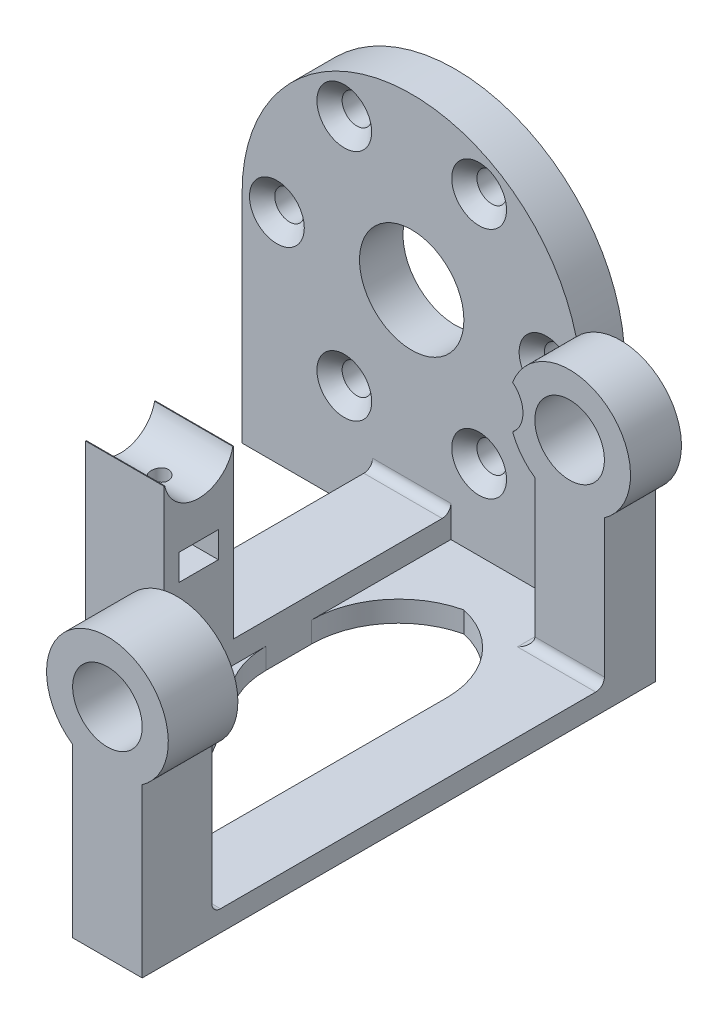
SolidWorks part; units mm, degrees
ref_plane "Front Plane" through (0, 0, 0) normal (0, 0, 1) x (1, 0, 0)
ref_plane "Top Plane" through (0, 0, 0) normal (0, 1, 0) x (1, 0, 0)
ref_plane "Right Plane" through (0, 0, 0) normal (1, 0, 0) x (0, 0, -1)
sketch "Sketch5" plane through (0, 0, 0) normal (0, 0, 1) x (1, 0, 0)
  line L0 (0, 0) -> (0, 15.5) construction
  circle A0 centre (0, 0) radius 19.5
  circle A1 centre (-7.75, 13.4234) radius 1.5
  circle A2 centre (0, 0) radius 6
  circle A3 centre (7.75, 13.4234) radius 1.5
  circle A4 centre (15.5, 0) radius 1.5
  circle A5 centre (7.75, -13.4234) radius 1.5
  circle A6 centre (-7.75, -13.4234) radius 1.5
  circle A7 centre (-15.5, 0) radius 1.5
  point P18 (0, 0)
  dimension "D2" = 3
  dimension "D3" = 39
  dimension "D4" = 12
  dimension "D1" = 15.5
  dimension "D5" = 6
extrude "Boss-Extrude1" add sketch "Sketch5" along normal blind 5
hole_wizard "CSK for M3 Flat Head Machine Screw1" positions "Sketch7" profile "Sketch6" countersink size "M3" standard "ANSI Metric" end condition through all
sketch "Sketch7" plane through (0, 0, 5) normal (0, 0, 1) x (1, 0, 0)
  point P0 (-15.5, 0)
  point P3 (-7.75, 13.4234)
  point P6 (7.75, 13.4234)
  point P9 (15.5, 0)
  point P12 (7.75, -13.4234)
  point P15 (-7.75, -13.4234)
sketch "Sketch6" plane through (-15.5, 0, 5) normal (1, 0, 0) x (0, -1, 0)
  line L0 (0, 0) -> (0, 5)
  line L1 (0, 5) -> (1.7, 5)
  line L2 (1.7, 5) -> (1.7, 1.45)
  line L3 (1.7, 1.45) -> (3.15, 0)
  line L5 (3.15, 0) -> (0, 0)
  line L6 (-1.7, 1.45) -> (-3.15, 0) construction
  line L11 (0, -6.35) -> (0, 107.95) construction
  dimension "Thru Hole Dia." = 3.4
  dimension "Thru Hole Depth" = 5
  dimension "Near C'Sink Dia." = 6.3
  dimension "Near C'Sink Angle" = 90
sketch "Sketch8" plane through (0, 0, 5) normal (0, 0, 1) x (1, 0, 0)
  line L0 (-19.5, 0) -> (-19.5, -25)
  line L1 (-19.5, -25) -> (19.5, -25)
  line L2 (19.5, -25) -> (19.5, 0)
  circle A0 centre (0, 0) radius 19.5 construction
  arc A1 (-19.5, 0) -> (19.5, 0) centre (0, 0) ccw
  dimension "D1" = 25
extrude "Boss-Extrude2" add sketch "Sketch8" against normal up to surface (5 mm away) up to face at (-13.8, 0, 0)
sketch "Sketch9" plane through (0, 0, 5) normal (0, 0, 1) x (1, 0, 0)
  line L0 (-19.5, -25) -> (19.5, -25) construction
  line L4 (-4.5, -20) -> (-4.5, -25)
  line L5 (4.5, -20) -> (-4.5, -25) construction
  line L6 (4.5, -25) -> (-4.5, -20) construction
  line L7 (-19.5, -25) -> (0, -22.5) construction
  line L8 (0, -22.5) -> (19.5, -25) construction
  line L9 (-4.5, -25) -> (4.5, -25)
  line L10 (-4.5, -20) -> (4.5, -20)
  line L11 (4.5, -20) -> (4.5, -25)
  point P0 (0, -22.5)
  dimension "D1" = 5
  dimension "D2" = 9
extrude "Boss-Extrude3" add sketch "Sketch9" along normal blind 32.9817
sketch "Sketch10" plane through (0.3712, -20, 0) normal (0, 1, 0) x (1, 0, 0)
  line L1 (-4.8712, -37.9817) -> (4.1288, -37.9817)
  line L2 (-4.8712, -37.9817) -> (-4.8712, -29.9817)
  line L3 (-4.8712, -29.9817) -> (4.1288, -29.9817)
  line L4 (4.1288, -37.9817) -> (4.1288, -29.9817)
  line L6 (-4.8712, -37.9817) -> (-4.8712, -5) construction
  line L7 (4.1288, -37.9817) -> (4.1288, -5) construction
  dimension "D1" = 8
extrude "Boss-Extrude4" add sketch "Sketch10" along normal blind 24
sketch "Sketch11" plane through (-4.5, 0, 0) normal (-1, 0, 0) x (0, 0, 1)
  line L0 (29.9817, 4) -> (29.9817, -20) construction
  line L2 (29.9817, 4) -> (37.9817, 4) construction
  line L3 (37.9817, 4) -> (37.9817, -25) construction
  line L4 (29.9817, 0) -> (27.1369, 2.0822)
  line L5 (27.1369, 2.0822) -> (27.3574, 4.8482)
  line L6 (27.3574, 4.8482) -> (32.7492, 5.4696)
  line L7 (32.7492, 5.4696) -> (41.4483, 5.0286)
  line L8 (41.4483, 5.0286) -> (40.8237, 2.383)
  line L9 (40.8237, 2.383) -> (37.9817, 0)
  line L10 (29.9817, -0.8) -> (30.0625, -0.8)
  line L11 (37.9009, -0.8) -> (37.9817, -0.8)
  line L12 (37.9817, 0) -> (37.9817, -0.8)
  line L13 (29.9817, -0.8) -> (29.9817, 0)
  arc A0 (30.0625, -0.8) -> (37.9009, -0.8) centre (33.9817, 0) ccw
  dimension "D1" = 0.8
extrude "Cut-Extrude1" cut sketch "Sketch11" against normal blind 20
sketch "Sketch12" plane through (0, -0.8, 0) normal (0, 1, 0) x (1, 0, 0)
  line L0 (-4.5, -29.9817) -> (4.5, -37.9817) construction
  line L1 (4.5, -29.9817) -> (-4.5, -37.9817) construction
  line L2 (4.5, -37.9009) -> (4.5, -30.0625) construction
  line L3 (4.5, -29.9817) -> (4.5, -5) construction
  circle A0 centre (0, -33.9817) radius 1
  dimension "D1" = 2
extrude "Cut-Extrude2" cut sketch "Sketch12" against normal blind 16
sketch "Sketch13" plane through (-4.5, 0, 0) normal (-1, 0, 0) x (0, 0, 1)
  line L0 (29.9817, -8.9707) -> (31.7317, -8.9707) construction
  line L1 (31.7317, -8.2443) -> (36.2317, -8.2443)
  line L2 (31.7317, -8.2443) -> (31.7317, -11.2443)
  line L3 (31.7317, -11.2443) -> (36.2317, -11.2443)
  line L4 (36.2317, -8.2443) -> (36.2317, -11.2443)
  line L5 (29.9817, -0.8) -> (29.9817, -20) construction
  line L6 (37.9817, -0.8) -> (37.9817, -25) construction
  line L7 (36.2317, -8.9707) -> (37.9817, -8.9707) construction
  dimension "D1" = 4.5
  dimension "D2" = 3
extrude "Cut-Extrude3" cut sketch "Sketch13" against normal up to surface (9 mm away) up to face at (4.5, -12.05, 26.7363)
sketch "Sketch14" plane through (0, -25, 0) normal (0, -1, 0) x (1, 0, 0)
  line L0 (4.5, 37.9817) -> (4.5, 5) construction
  line L1 (4.5, 5) -> (28.015, 5)
  line L2 (4.5, 5) -> (4.5, 11)
  line L3 (4.5, 11) -> (20.015, 11)
  line L4 (28.015, 5) -> (28.015, 12.4921)
  line L5 (28.015, -11.9618) -> (28.015, 22.5232) construction
  line L6 (20.015, 70.0082) -> (20.015, 35.5232) construction
  line L8 (28.015, 12.4921) -> (28.015, 64)
  line L9 (28.015, 64) -> (20.015, 64)
  line L10 (20.015, 11) -> (20.015, 64)
  line L12 (4.5, 5) -> (19.5, 5) construction
  dimension "D1" = 0
  dimension "D2" = 6
  dimension "D3" = 59
extrude "Boss-Extrude5" add sketch "Sketch14" against normal blind 2.4
sketch "Sketch15" plane through (28.015, 0, 0) normal (1, 0, 0) x (0, 0, -1)
  line L0 (-38.5232, 4) -> (-70.0082, 4) construction
  line L1 (-64, -22.6) -> (-56, -22.6)
  line L2 (-64, -22.6) -> (-64, 4)
  line L3 (-64, 4) -> (-56, 4)
  line L4 (-56, -22.6) -> (-56, 4)
  line L6 (-5, -22.6) -> (-13, -22.6)
  line L7 (-5, -22.6) -> (-5, 4)
  line L8 (-5, 4) -> (-13, 4)
  line L9 (-13, -22.6) -> (-13, 4)
  dimension "D1" = 8
extrude "Boss-Extrude6" add sketch "Sketch15" against normal up to surface (8 mm away) up to face at (20.015, -23.8, 37.5)
sketch "Sketch16" plane through (0, 0, 64) normal (0, 0, 1) x (1, 0, 0)
  line L0 (20.015, -1.0579) -> (20.1574, -1.0579)
  line L1 (20.015, 4) -> (20.015, -25) construction
  line L2 (28.015, 4) -> (28.015, -25) construction
  line L3 (28.015, -1.0579) -> (30.9797, 0.9089)
  line L4 (30.9797, 0.9089) -> (30.0419, 7.8056)
  line L5 (20.015, -1.0579) -> (20.015, 10.6199)
  line L6 (20.015, 5.7446) -> (20.015, 15.4952) construction
  line L7 (20.015, 10.6199) -> (30.0419, 7.8056)
  line L8 (27.8726, -1.0579) -> (28.015, -1.0579)
  arc A0 (20.1574, -1.0579) -> (27.8726, -1.0579) centre (24.015, 0) ccw
extrude "Cut-Extrude4" cut sketch "Sketch16" against normal up to surface (59 mm away) up to face at (22.51, -14.5333, 5)
sketch "Sketch17" plane through (0, -22.6, 0) normal (0, 1, 0) x (1, 0, 0)
  line L0 (20.015, -56) -> (20.015, -13) construction
  line L1 (20.015, -13.8581) -> (28.015, -13.8581)
  line L2 (20.015, -13.8581) -> (20.015, -10.8581)
  line L3 (20.015, -10.8581) -> (28.015, -10.8581)
  line L4 (28.015, -13.8581) -> (28.015, -10.8581)
  line L5 (28.015, -5) -> (28.015, -13) construction
  dimension "D1" = 3
extrude "Cut-Extrude5" cut sketch "Sketch17" along normal up to surface (21.5421 mm away) up to face at (20.0862, -1.0579, 9)
sketch "Sketch19" plane through (0, 0, 29.9817) normal (0, 0, -1) x (-1, 0, 0)
  circle A0 centre (-7.75, -13.4234) radius 3
  dimension "D1" = 6
extrude "Cut-Extrude6" [suppressed] cut sketch "Sketch19" against normal through all
sketch "Sketch20" plane through (0, -22.6, 0) normal (0, 1, 0) x (1, 0, 0)
  line L0 (20.015, -64) -> (4.5, -37.9817)
  line L1 (20.015, -55) -> (4.5, -28.9817)
  line L2 (20.015, -56) -> (20.015, -11) construction
  line L3 (4.5, -29.9817) -> (4.5, -5) construction
  line L4 (4.5, -28.9817) -> (4.5, -37.9817)
  line L5 (20.015, -55) -> (20.015, -64)
  dimension "D1" = 9
extrude "Boss-Extrude7" add sketch "Sketch20" against normal up to surface (2.4 mm away) up to face at (8.005, -25, 20.4969)
fillet "Fillet1" radius 10 3 edges at (20.015, -23.8, 11) (4.5, -23.8, 11) (4.5, -23.8, 28.9817)
fillet "Fillet2" radius 1 1 edges at (20.015, -23.8, 55)
fillet "Fillet3" radius 1 5 edges at (0, -20, 5) (20.015, -22.6, 60) (20.015, -22.6, 7.9291) (24.015, -22.6, 10.8581) (24.015, -22.6, 56)
sketch "Sketch22" plane through (28.015, 0, 0) normal (1, 0, 0) x (0, 0, -1)
  circle A0 centre (-60, -7.7015) radius 1
extrude "Cut-Extrude7" [suppressed] cut sketch "Sketch22" against normal up to surface (8 mm away) up to face at (20.015, -11.329, 60)
sketch "Sketch23" plane through (28.015, 0, 0) normal (1, 0, 0) x (0, 0, -1)
  circle A0 centre (-7.9291, -7.7015) radius 1
extrude "Cut-Extrude8" [suppressed] cut sketch "Sketch23" against normal up to surface (8 mm away) up to face at (20.015, -11.329, 7.9291)
sketch "Sketch24" plane through (0, 0, 5) normal (0, 0, -1) x (-1, 0, 0)
  line L0 (-20.015, -21.6) -> (-20.015, -1.0579) construction
  line L1 (-28.015, -1.0579) -> (-28.015, -25) construction
  line L4 (-20.015, -5.7446) -> (-20.015, -1.0579)
  line L5 (-28.015, -1.0579) -> (-28.015, -5.7446)
  line L6 (-27.8726, -1.0579) -> (-28.015, -1.0579)
  line L7 (-20.015, -1.0579) -> (-20.1574, -1.0579)
  arc A0 (-20.1574, -1.0579) -> (-27.8726, -1.0579) centre (-24.015, 0) ccw
  arc A1 (-20.015, -5.7446) -> (-17.4629, -2.4637) centre (-24.015, 0) ccw
  circle A2 centre (-15.5, 0) radius 3.15 construction
  arc A3 (-17.4629, 2.4637) -> (-17.4629, -2.4637) centre (-15.5, 0) ccw
  arc A4 (-17.4629, 2.4637) -> (-28.015, -5.7446) centre (-24.015, 0) ccw
  dimension "D1" = 14
extrude "Boss-Extrude8" add sketch "Sketch24" against normal up to surface (5.8581 mm away) up to face at (24.015, -8.3956, 10.8581)
sketch "Sketch25" plane through (0, 0, 64) normal (0, 0, 1) x (1, 0, 0)
  line L0 (20.015, -5.7446) -> (20.015, -1.0579)
  line L1 (20.015, -1.0579) -> (20.1574, -1.0579)
  line L2 (27.8726, -1.0579) -> (28.015, -1.0579)
  line L3 (28.015, -1.0579) -> (28.015, -5.7446)
  circle A0 centre (24.015, 0) radius 4 construction
  arc A2 (27.8726, -1.0579) -> (20.1574, -1.0579) centre (24.015, 0) ccw
  arc A3 (28.015, -5.7446) -> (20.015, -5.7446) centre (24.015, 0) ccw
extrude "Boss-Extrude9" add sketch "Sketch25" against normal up to surface (8 mm away) up to face at (24.015, -8.3956, 56)
